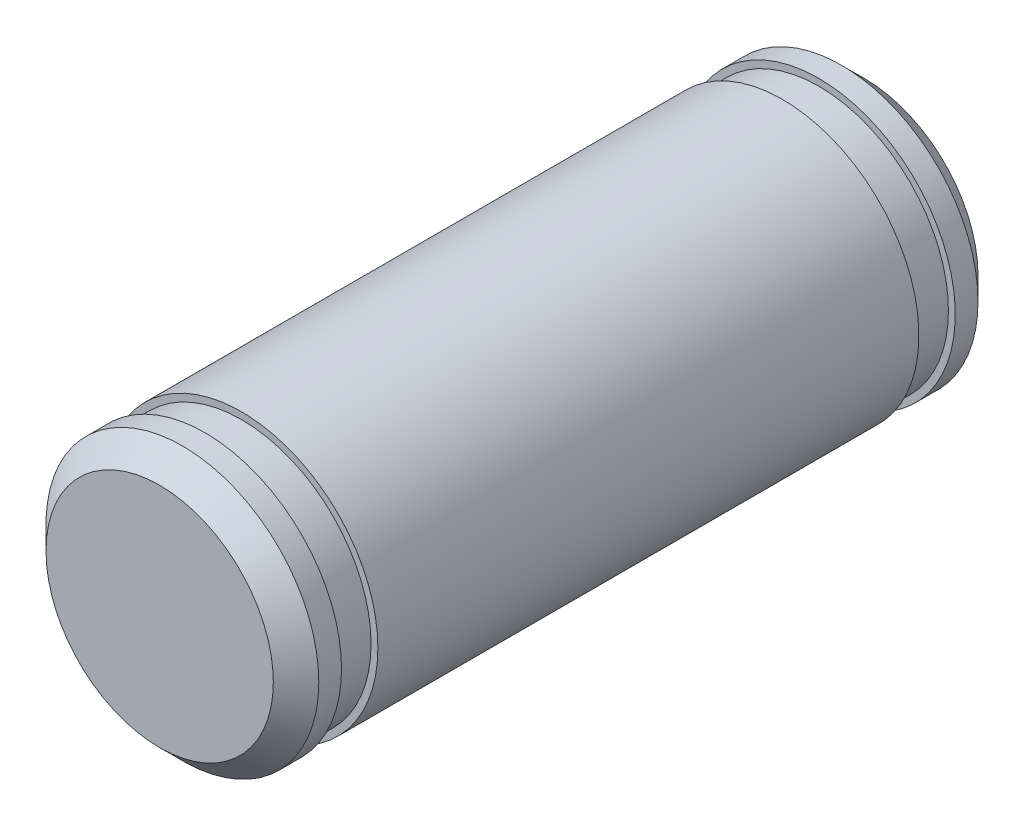
SolidWorks part; units mm, degrees
material "Stop 1060"
ref_plane "Płaszczyzna przednia" through (0, 0, 0) normal (0, 0, 1) x (1, 0, 0)
ref_plane "Płaszczyzna górna" through (0, 0, 0) normal (0, 1, 0) x (1, 0, 0)
ref_plane "Płaszczyzna prawa" through (0, 0, 0) normal (1, 0, 0) x (0, 0, -1)
sketch "Szkic1" plane through (0, 0, 0) normal (0, 0, 1) x (1, 0, 0)
  circle A0 centre (0, 0) radius 3
  dimension "D1" = 6
extrude "Dodanie-wyciągnięcie1" add sketch "Szkic1" along normal blind 15.5
chamfer "Sfazowanie1" distance 0.5 angle 45 2 edges at (3, 0, 0) (3, 0, 15.5)
sketch "Szkic2" plane through (0, 0, 15.5) normal (0, 0, 1) x (1, 0, 0)
  circle A0 centre (0, 0) radius 3
  circle A1 centre (0, 0) radius 2.85
  dimension "D1" = 6
  dimension "D2" = 5.7
extrude "Wytnij-wyciągnięcie1" cut sketch "Szkic2" against normal blind 0.8 from offset 1 offset against normal yes
sketch "Szkic3" plane through (0, 0, 0) normal (0, 0, -1) x (-1, 0, 0)
  circle A0 centre (0, 0) radius 3
  circle A1 centre (0, 0) radius 2.85
  dimension "D1" = 5.7
  dimension "D2" = 6
extrude "Wytnij-wyciągnięcie2" cut sketch "Szkic3" against normal blind 0.8 from offset 1 offset against normal yes
